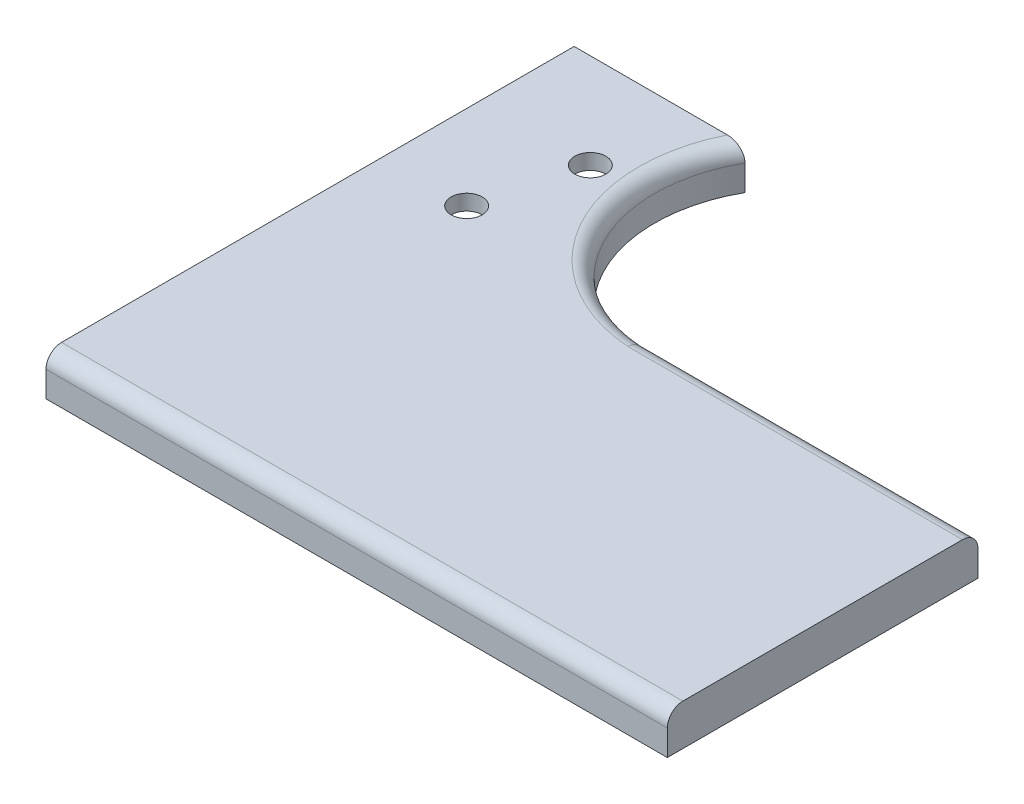
SolidWorks part; units mm, degrees
ref_plane "Alzado" through (0, 0, 0) normal (0, 0, 1) x (1, 0, 0)
ref_plane "Planta" through (0, 0, 0) normal (0, 1, 0) x (1, 0, 0)
ref_plane "Vista lateral" through (0, 0, 0) normal (1, 0, 0) x (0, 0, -1)
sketch "Croquis14" plane through (0, 0, 0) normal (0, 1, 0) x (1, 0, 0)
  line L0 (20, 10) -> (-1.5, 10)
  line L1 (-20, -10) -> (20, -10)
  line L2 (-20, -10) -> (-20, 10)
  line L3 (-20, 10) -> (-20, 24)
  line L4 (20, -10) -> (20, 10)
  line L5 (-20, -10) -> (20, 10) construction
  line L6 (-20, 10) -> (20, -10) construction
  line L7 (-20, 24) -> (-9, 24)
  arc A0 (-9, 24) -> (-1.5, 10) centre (-0.8, 19.3839) ccw
  point P0 (0, 0)
  dimension "D6" = 9.41
  dimension "D1" = 40
  dimension "D2" = 20
  dimension "D3" = 21.5
  dimension "D4" = 14
  dimension "D5" = 11
extrude "Saliente-Extruir1" add sketch "Croquis14" along normal blind 2.8
shell "Vaciado2" thickness 1 removed face at (-2.3908, 0, -7.6567)
sketch "Croquis27" plane through (0, 0, 0) normal (0, -1, 0) x (1, 0, 0)
  line L1 (-21.9771, 11.9094) -> (25.0951, 11.9094)
  line L2 (-21.9771, 11.9094) -> (-21.9771, -25.9094)
  line L3 (-21.9771, -25.9094) -> (25.0951, -25.9094)
  line L4 (25.0951, 11.9094) -> (25.0951, -25.9094)
extrude "Cortar-Extruir10" cut sketch "Croquis27" against normal blind 0.15
sketch "Croquis28" plane through (0, 1.8, 0) normal (0, -1, 0) x (1, 0, 0)
  circle A0 centre (-12.8572, -17.9) radius 1
  circle A1 centre (-14.5685, -11.6502) radius 1
  dimension "D1" = 2
  dimension "D2" = 2
extrude "Cortar-Extruir11" cut sketch "Croquis28" against normal blind 10
fillet "Redondeo6" radius 1 2 edges at (-9.0947, 2.8, -14.9403) (9.25, 2.8, -10)
fillet "Fillet1" radius 1 1 edges at (0, 2.8, 10)
